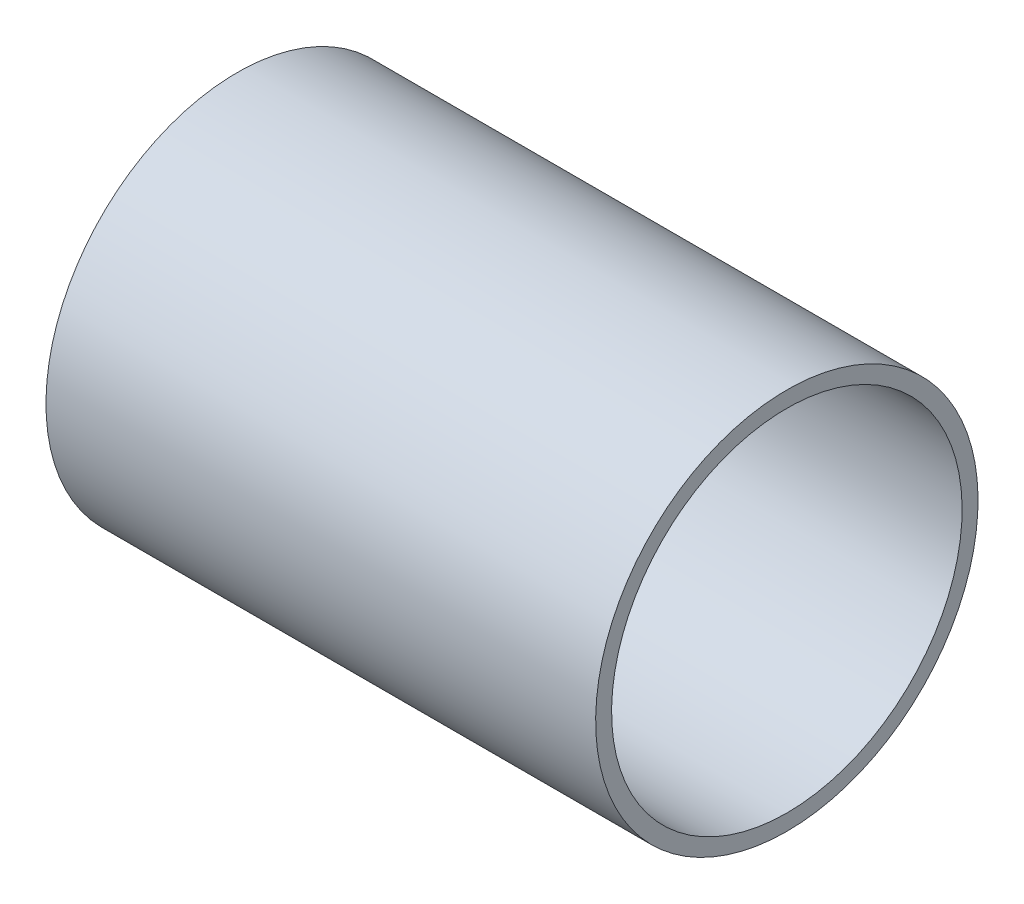
SolidWorks part; units mm, degrees
ref_plane "Front Plane" through (0, 0, 0) normal (0, 0, 1) x (1, 0, 0)
ref_plane "Top Plane" through (0, 0, 0) normal (0, 1, 0) x (1, 0, 0)
ref_plane "Right Plane" through (0, 0, 0) normal (1, 0, 0) x (0, 0, -1)
sketch "Sketch1" plane through (0, 0, 0) normal (0, 0, 1) x (1, 0, 0)
  line L0 (-66.5775, 0) -> (66.5775, 0) construction
  line L1 (-17.25, 12) -> (17.25, 12)
  line L2 (-17.25, 12) -> (-17.25, 11)
  line L3 (-17.25, 11) -> (17.25, 11)
  line L4 (17.25, 11) -> (17.25, 12)
  point P3 (0, 0)
  point P6 (0, 12)
  dimension "D1" = 24
  dimension "D2" = 1
  dimension "D3" = 34.5
revolve "Revolve1" add sketch "Sketch1" angle 360 about L0
